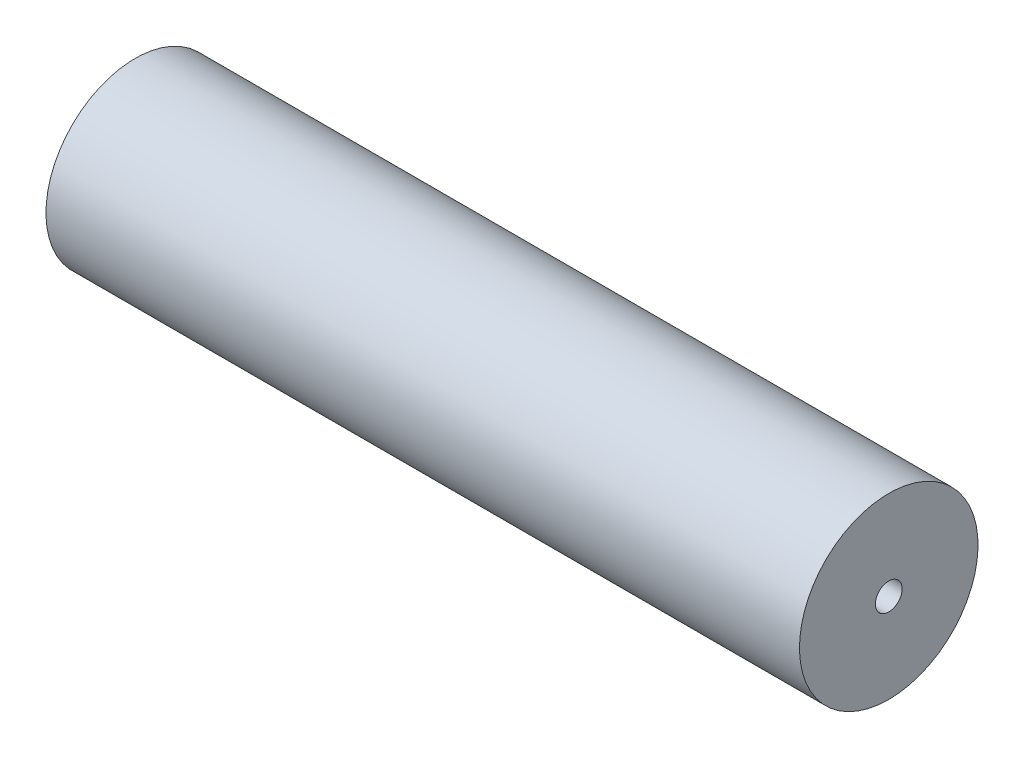
SolidWorks part; units mm, degrees
ref_plane "Plan de face" through (0, 0, 0) normal (0, 0, 1) x (1, 0, 0)
ref_plane "Plan de dessus" through (0, 0, 0) normal (0, 1, 0) x (1, 0, 0)
ref_plane "Plan de droite" through (0, 0, 0) normal (1, 0, 0) x (0, 0, -1)
sketch "Esquisse1" plane through (0, 0, 0) normal (0, 0, 1) x (1, 0, 0)
  line L0 (-63.3, 0) -> (75.2437, 0) construction
  line L2 (-63.3, 15) -> (-63.3, 0)
  line L4 (-63.3, 15) -> (63.3, 15)
  line L5 (-63.3, 0) -> (63.3, 0)
  line L6 (0, 15) -> (0, 0) construction
  line L7 (63.3, 2.5) -> (63.3, 15)
  line L9 (63.3, 0) -> (63.3, 2.5)
  dimension "D4" = 15
revolve "Révolution1" add sketch "Esquisse1" angle 360 about L5
sketch "Esquisse2" plane through (63.3, 0, 0) normal (1, 0, 0) x (0, 0, -1)
  circle A0 centre (0, 0) radius 2.25
extrude "Enlèv. mat.-Extru.1" cut sketch "Esquisse2" against normal up to body
